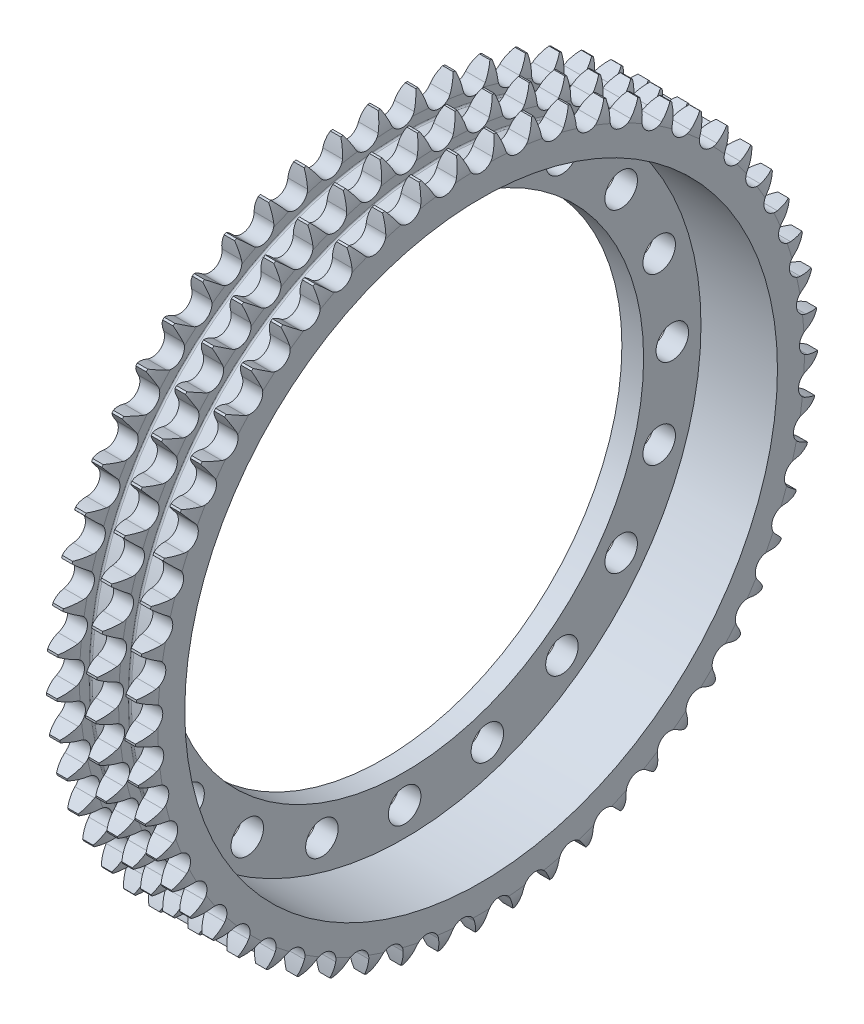
SolidWorks part; units mm, degrees
material "1.0503 (C45)"
ref_plane "Plane1" through (0, 0, 0) normal (0, 0, 1) x (1, 0, 0)
ref_plane "Plane2" through (0, 0, 0) normal (0, 1, 0) x (1, 0, 0)
ref_plane "Plane3" through (0, 0, 0) normal (1, 0, 0) x (0, 0, -1)
sketch "Clipboard" plane through (0, 0, 0) normal (0, 1, 0) x (1, 0, 0)
  line L0 (0, 0) -> (5.1877, -7.9883)
  line L1 (-15, 0) -> (100, 0) construction
  line L2 (0, 0) -> (-0.8203, 0.9272)
  line L3 (0, 0) -> (-8.8973, 3.4006)
  line L4 (0, 0) -> (1.6884, 2.5999)
  line L5 (0, 0) -> (-46.8476, -17.4728)
  line L6 (0, 0) -> (-21.2921, -14.3658)
  line L7 (-0.8203, 0.9272) -> (24.1799, 44.2289)
  line L8 (-76.2, 38.1) -> (-75.5, 38.1)
  line L9 (-73.319, 40.6764) -> (-72.9207, 40.7126)
  line L10 (-73.4529, 9.1872) -> (-63.2129, 9.1872)
  circle A0 centre (0, 0) radius 3.175
  circle A1 centre (0, 0) radius 37.5
  circle A2 centre (0, 0) radius 37.5
  dimension "Dr" = 6.35
  dimension "MHD" = 75
  dimension "Hub_dia" = 75
  dimension "Num_teeth" = 57
  dimension "Pitch" = 9.525
  dimension "Width" = 3.1
  dimension "Side_relief" = 1.238
  dimension "Side_radius" = 9.525
  dimension "Overall_len" = 50
  dimension "Show_teeth" = 57
  dimension "Thickness" = 25.6852
  dimension "OAL" = 50.0005
  dimension "T_dim" = 0.7
  dimension "Fillet_rad" = 0.4
  dimension "Face_width" = 5.205
  dimension "Num_strands" = 3
  dimension "Transv_pitch" = 10.24
  dimension "Plate_wid" = 8.26
sketch "BasProSke" plane through (0, 0, 0) normal (0, 1, 0) x (1, 0, 0)
  line L0 (-10, 0) -> (60, 0) construction
  line L1 (0, 0) -> (0, 84.5352)
  line L2 (0, 0) -> (25.6852, 0)
  line L3 (25.6852, 0) -> (25.6852, 84.5352)
  line L4 (24.4472, 89.2311) -> (1.238, 89.2311)
  arc A0 (0, 84.5352) -> (1.238, 89.2311) centre (9.525, 84.5352) cw
  arc A1 (25.6852, 84.5352) -> (24.4472, 89.2311) centre (16.1602, 84.5352) ccw
  dimension "Thickness" = 25.6852
  dimension "D1" = 9.525
  dimension "G1" = 1.238
  dimension "G2" = 1.238
  dimension "Diameter" = 178.4622
revolve "Base-Revolve" add sketch "BasProSke" angle 360 about L0
sketch "GrvSke" plane through (0, 0, 0) normal (0, 1, 0) x (1, 0, 0)
  line L0 (5.2052, 84.5352) -> (5.2052, 82.0465)
  line L1 (5.6052, 81.6465) -> (9.84, 81.6465)
  line L2 (10.24, 82.0465) -> (10.24, 84.5352)
  line L3 (3.9672, 89.2311) -> (11.478, 89.2311)
  line L4 (7.7226, 0) -> (7.7226, 52.07) construction
  line L5 (-10, 0) -> (60, 0) construction
  line L6 (0, 0) -> (35.56, 0) construction
  arc A0 (10.24, 84.5352) -> (11.478, 89.2311) centre (19.765, 84.5352) cw
  arc A1 (5.2052, 84.5352) -> (3.9672, 89.2311) centre (-4.3198, 84.5352) ccw
  arc A2 (5.2052, 82.0465) -> (5.6052, 81.6465) centre (5.6052, 82.0465) ccw
  arc A3 (9.84, 81.6465) -> (10.24, 82.0465) centre (9.84, 82.0465) ccw
  dimension "Fillet_rad" = 0.4
  dimension "D1" = 9.525
  dimension "G1" = 1.238
  dimension "Diameter" = 178.4622
  dimension "Grv_diam" = 163.293
  dimension "Offset" = 7.7226
  dimension "Grv_width" = 5.0348
revolve "Groove" cut sketch "GrvSke" angle 360 about L6
pattern_linear "Grooves" count 2 spacing 10.24 along (1, 0, 0) of "Groove"
sketch "TooCutSke" plane through (0, 0, 0) normal (1, 0, 0) x (0, 0, -1)
  line L0 (0, 86.4847) -> (2.998, 85.3465) construction
  line L1 (0, 0) -> (0, 107) construction
  line L2 (0, 86.4847) -> (-10, 86.4847) construction
  line L3 (0, 86.4847) -> (-2.998, 85.3465) construction
  arc A0 (2.998, 85.3465) -> (4.8691, 89.5989) centre (45.0288, 69.3893) cw
  arc A1 (2.998, 85.3465) -> (-2.998, 85.3465) centre (0, 86.4847) cw
  arc A2 (-2.998, 85.3465) -> (-4.8691, 89.5989) centre (-45.0288, 69.3893) ccw
  arc A3 (4.8691, 89.5989) -> (-4.8691, 89.5989) centre (0, 0) ccw
  dimension "R1" = 3.2067
  dimension "R2" = 44.958
  dimension "Overcut" = 89.7311
  dimension "Seat_radius" = 86.4847
  dimension "X" = 138.421
extrude "ToothCut" cut sketch "TooCutSke" along normal through all
pattern_circular "TeethCuts" count 57 every 6.316 about axis through (-10, 0, 0) along (1, 0, 0) of "ToothCut"
sketch "HubNeaOneSke" plane through (0, 0, 0) normal (-1, 0, 0) x (0, 0, 1)
  circle A0 centre (0, 0) radius 37.5
  dimension "Diameter" = 75
extrude "HubNearOne" [suppressed] add sketch "HubNeaOneSke" along normal blind 24.3153
fillet "HubNearOneFillet" [suppressed] radius 0.4
sketch "HubNeaBotSke" plane through (0, 0, 0) normal (-1, 0, 0) x (0, 0, 1)
  circle A0 centre (0, 0) radius 37.5
  dimension "Diameter" = 75
extrude "HubNearBoth" [suppressed] add sketch "HubNeaBotSke" along normal blind 12.1577
fillet "HubNearBothFillet" [suppressed] radius 0.4
ref_plane "FarPln" through (25.6852, 0, 0) normal (1, 0, 0) x (0, 0, -1)
sketch "HubFarSke" plane through (25.6852, 0, 0) normal (1, 0, 0) x (0, 0, -1)
  circle A0 centre (0, 0) radius 37.5
  dimension "Diameter" = 75
extrude "HubFar" [suppressed] add sketch "HubFarSke" along normal blind 12.1577
fillet "HubFarFillet" [suppressed] radius 0.4
sketch "BorSke" plane through (0, 0, 0) normal (1, 0, 0) x (0, 0, -1)
  circle A0 centre (0, 0) radius 2
  dimension "Diameter" = 4
extrude "Bore" cut sketch "BorSke" along normal mid plane 100.001
sketch "KeySke" plane through (0, 0, 0) normal (1, 0, 0) x (0, 0, -1)
  line L0 (-0.8, 0) -> (-0.8, 2.7)
  line L1 (-0.8, 2.7) -> (0.8, 2.7)
  line L2 (0.8, 2.7) -> (0.8, 0)
  line L3 (0, 0) -> (0, 34) construction
  line L4 (-0.8, 0) -> (0.8, 0)
  dimension "Offset" = 2.7
  dimension "Width" = 1.6
extrude "Keyway" [suppressed] cut sketch "KeySke" along normal mid plane 100.001
pattern_circular "Keyway2" [suppressed] count 2 every 90 about axis through (-10, 0, 0) along (1, 0, 0)
sketch "Sketch1" plane through (25.6852, 0, 0) normal (1, 0, 0) x (0, 0, -1)
  circle A0 centre (0, 0) radius 62.5
  circle A1 centre (0, 70) radius 4.25
  circle A2 centre (0, 0) radius 70 construction
  circle A3 centre (-66.574, 21.6312) radius 4.25
  circle A4 centre (21.6312, 66.574) radius 4.25
  circle A5 centre (41.145, 56.6312) radius 4.25
  circle A6 centre (56.6312, 41.145) radius 4.25
  circle A7 centre (66.574, 21.6312) radius 4.25
  circle A8 centre (70, 0) radius 4.25
  circle A9 centre (66.574, -21.6312) radius 4.25
  circle A10 centre (56.6312, -41.145) radius 4.25
  circle A11 centre (41.145, -56.6312) radius 4.25
  circle A12 centre (21.6312, -66.574) radius 4.25
  circle A13 centre (0, -70) radius 4.25
  circle A14 centre (-21.6312, -66.574) radius 4.25
  circle A15 centre (-41.145, -56.6312) radius 4.25
  circle A16 centre (-56.6312, -41.145) radius 4.25
  circle A17 centre (-66.574, -21.6312) radius 4.25
  circle A18 centre (-70, 0) radius 4.25
  circle A19 centre (-56.6312, 41.145) radius 4.25
  circle A20 centre (-41.145, 56.6312) radius 4.25
  circle A21 centre (-21.6312, 66.574) radius 4.25
  point P40 (0, 0)
  dimension "D1" = 125
  dimension "D2" = 8.5
  dimension "D3" = 140
  dimension "D4" = 20
extrude "Cut-Extrude1" cut sketch "Sketch1" against normal through all
sketch "Sketch3" plane through (25.6852, 0, 0) normal (1, 0, 0) x (0, 0, -1)
  circle A0 centre (0, 0) radius 77.5
  dimension "D1" = 155
extrude "Cut-Extrude5" cut sketch "Sketch3" against normal blind 20
equation "' \"Pitch@Clipboard\" = 12.7"
equation "' \"Num_strands@Clipboard\" = 3"
equation "' \"Num_teeth@Clipboard\" = 9"
equation "' \"Hub_dia@Clipboard\" = 50"
equation "' \"Overall_len@Clipboard\" = 3"
equation "' \"Diameter@BorSke\" = 12"
equation "' \"T_dim@Clipboard\" = 1"
equation "' \"Width@KeySke\" = 2"
equation "' \"Dr@Clipboard\" = 8.51"
equation "' \"Face_width@Clipboard\" = 7.2"
equation "' \"Side_radius@Clipboard\" = 12.7"
equation "' \"Side_relief@Clipboard\" = 1.27"
equation "' \"Transv_pitch@Clipboard\" = 13.92"
equation "' \"Show_teeth@Clipboard\" = 9"
equation "' \"Fillet_rad@Clipboard\" = 0.6"
equation "' \"Plate_wid@Clipboard\" = 11.8"
equation "\"Num_teeth@Clipboard\" = int( \"Num_teeth@Clipboard\" )"
equation "\"Num_teeth@Clipboard\" = ((sgn( \"Num_teeth@Clipboard\" - 5.0)+1)*( \"Num_teeth@Clipboard\" - 5.0))/2 +5.0"
equation "\"Num_teeth@Clipboard\" = ((sgn( \"Num_teeth@Clipboard\" - 200.0)-1)*( \"Num_teeth@Clipboard\" - 200.0))/-2 +200.0"
equation "\"MHD@Clipboard\" = \"Pitch@Clipboard\" * (1.0 / tan(3.14159265 / \"Num_teeth@Clipboard\" )) - 1.05 * \"Plate_wid@Clipboard\" - 0.76"
equation "\"Thickness@Clipboard\"  = \"Face_width@Clipboard\" + (\"Num_strands@Clipboard\" - 1) * \"Transv_pitch@Clipboard\""
equation "\"OAL@Clipboard\" = \"Thickness@Clipboard\" + 2 * \"Fillet_rad@Clipboard\" + 1"
equation "\"MHD@Clipboard\" = ((sgn( \"MHD@Clipboard\" - \"Hub_dia@Clipboard\" )-1)*( \"MHD@Clipboard\" - \"Hub_dia@Clipboard\" ))/-2+ \"Hub_dia@Clipboard\""
equation "\"OAL@Clipboard\" = ((sgn( \"OAL@Clipboard\" - \"Overall_len@Clipboard\" )+1)*( \"OAL@Clipboard\" - \"Overall_len@Clipboard\" ))/2 + \"Overall_len@Clipboard\" + 0.0005"
equation "\"Num_teeth@TeethCuts\" = int( \"Show_teeth@Clipboard\" ) + 1"
equation "\"Num_teeth@TeethCuts\" = ((sgn( \"Num_teeth@TeethCuts\" - \"Num_teeth@Clipboard\" )-1)*( \"Num_teeth@TeethCuts\" - \"Num_teeth@Clipboard\" ))/-2+ \"Num_teeth@Clipboard\""
equation "\"Num_teeth@TeethCuts\" = ((sgn( \"Num_teeth@TeethCuts\" - 2.0)+1)*( \"Num_teeth@TeethCuts\" - 2.0))/2 +2.0"
equation "\"Angle@TeethCuts\" = 360.0 / \"Num_teeth@Clipboard\""
equation "\"Seat_radius@TooCutSke\" = ( \"Pitch@Clipboard\" / 2.0) / sin(3.14159265 / \"Num_teeth@Clipboard\" ) - \"Dr@Clipboard\" / 2.0 + \"Dr@Clipboard\" * 0.505"
equation "\"R1@TooCutSke\"  = \"Dr@Clipboard\" * 0.505"
equation "\"X@TooCutSke\" = 140.0 - (90.0 / \"Num_teeth@Clipboard\")"
equation "\"R2@TooCutSke\" = 0.12 * \"Dr@Clipboard\" * ( \"Num_teeth@Clipboard\" + 2.0)"
equation "\"Overcut@TooCutSke\" = 0.5 + 0.625 * \"Pitch@Clipboard\" - 0.5 * \"Dr@Clipboard\"  +  \"Pitch@Clipboard\" / 2.0 / sin(3.14159265 / \"Num_teeth@Clipboard\" )"
equation "\"Diameter@BasProSke\" = 2.0 * ( 0.625 * \"Pitch@Clipboard\" - 0.5 * \"Dr@Clipboard\"  +  \"Pitch@Clipboard\" / 2.0 / sin(3.14159265 / \"Num_teeth@Clipboard\" ))"
equation "\"Thickness@BasProSke\"  = \"Thickness@Clipboard\""
equation "\"G1@BasProSke\" =  \"Side_relief@Clipboard\""
equation "\"G2@BasProSke\" =  \"Side_relief@Clipboard\""
equation "\"D1@BasProSke\" =  \"Side_radius@Clipboard\""
equation "\"Diameter@GrvSke\" = \"Diameter@BasProSke\""
equation "\"G1@GrvSke\" = \"Side_relief@Clipboard\""
equation "\"D1@GrvSke\" = \"Side_radius@Clipboard\""
equation "\"Grv_diam@GrvSke\" =  \"Pitch@Clipboard\" * (1.0 / tan(3.14159265 / \"Num_teeth@Clipboard\" ))- 1.04 * \"Plate_wid@Clipboard\" - 0.76"
equation "\"Grv_width@GrvSke\" =  \"Transv_pitch@Clipboard\" - \"Face_width@Clipboard\""
equation "\"Offset@GrvSke\" = \"Grv_width@GrvSke\" / 2.0 + \"Face_width@Clipboard\""
equation "\"Fillet_rad@GrvSke\" = \"Fillet_rad@Clipboard\""
equation "\"Offset@Grooves\" = \"Transv_pitch@Clipboard\""
equation "\"Num_grvs@Grooves\" = \"Num_strands@Clipboard\""
equation "\"Num_grvs@Grooves\" = \"Num_grvs@Grooves\" - 1 * sgn( \"Num_grvs@Grooves\" -1)"
equation "\"Diameter@HubNeaOneSke\" = \"MHD@Clipboard\""
equation "\"Length@HubNearOne\" = \"OAL@Clipboard\" - \"Thickness@BasProSke\""
equation "\"Diameter@HubNeaBotSke\" = \"MHD@Clipboard\""
equation "\"Length@HubNearBoth\" = ( \"OAL@Clipboard\" - \"Thickness@BasProSke\" ) / 2.0"
equation "\"D1@HubNearOneFillet\" = \"Fillet_rad@Clipboard\""
equation "\"D1@HubNearBothFillet\" = \"Fillet_rad@Clipboard\""
equation "\"Thickness@FarPln\" = \"Thickness@BasProSke\""
equation "\"Diameter@HubFarSke\" = \"MHD@Clipboard\""
equation "\"Length@HubFar\" = ( \"OAL@Clipboard\" - \"Thickness@BasProSke\" ) / 2.0"
equation "\"D1@HubFarFillet\" = \"Fillet_rad@Clipboard\""
equation "\"D1@Bore\" = \"OAL@Clipboard\" * 2.0"
equation "\"D1@Keyway\" = \"OAL@Clipboard\" * 2.0"
equation "\"Offset@KeySke\" = \"T_dim@Clipboard\" + \"Diameter@BorSke\" / 2.0"
